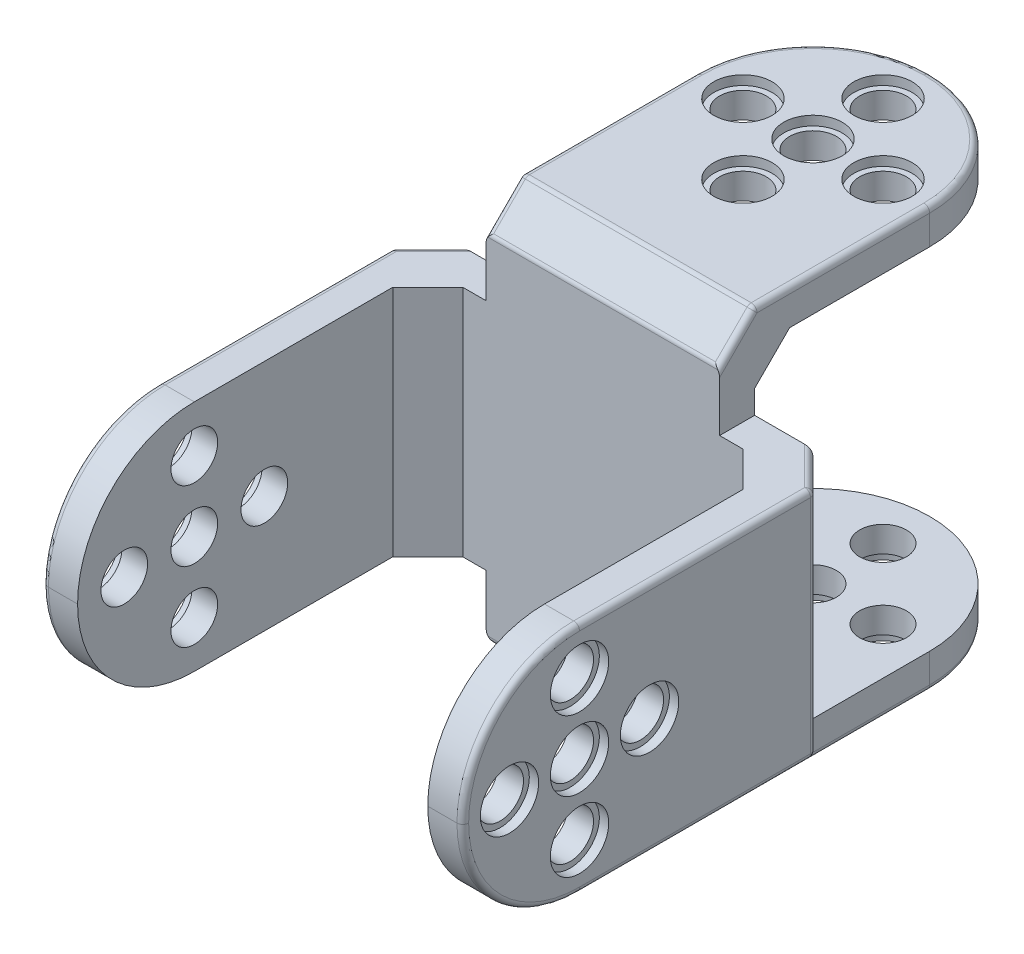
SolidWorks part; units mm, degrees
ref_plane "Front Plane" through (0, 0, 0) normal (0, 0, 1) x (1, 0, 0)
ref_plane "Top Plane" through (0, 0, 0) normal (0, 1, 0) x (1, 0, 0)
ref_plane "Right Plane" through (0, 0, 0) normal (1, 0, 0) x (0, 0, -1)
sketch "Sketch1" plane through (0, 0, 0) normal (0, 0, 1) x (1, 0, 0)
  line L1 (-18, 10) -> (18, 10)
  line L2 (-18, 10) -> (-18, -10)
  line L3 (-18, -10) -> (18, -10)
  line L4 (18, 10) -> (18, -10)
  line L5 (-18, 10) -> (18, -10) construction
  line L6 (-18, -10) -> (18, 10) construction
  line L7 (-10, -18) -> (10, -18)
  line L8 (-10, -18) -> (-10, 18)
  line L9 (-10, 18) -> (10, 18)
  line L10 (10, -18) -> (10, 18)
  line L11 (-10, -18) -> (10, 18) construction
  line L12 (-10, 18) -> (10, -18) construction
  point P0 (0, 0)
  point P6 (0, 0)
  dimension "D1" = 36
  dimension "D2" = 20
  dimension "D3" = 36
  dimension "D4" = 20
extrude "Boss-Extrude1" add sketch "Sketch1" along normal blind 3 contours L8 L9 L10 L7 | L1 L4 L3 L2
sketch "Sketch2" plane through (0, 0, 0) normal (0, 0, -1) x (-1, 0, 0)
  line L0 (10, 10) -> (10, 18) construction
  line L1 (-10, 18) -> (10, 18)
  line L2 (-10, 18) -> (-10, 15)
  line L3 (-10, 15) -> (10, 15)
  line L4 (10, 18) -> (10, 15)
  dimension "D1" = 3
extrude "Boss-Extrude2" add sketch "Sketch2" along normal blind 25
chamfer "Chamfer1" distance 3 angle 45 2 edges at (0, 18, 3)
fillet "Fillet1" radius 10 1 edges at (10, 16.5, -25)
fillet "Fillet2" radius 10 1 edges at (-10, 16.5, -25)
sketch "Sketch3" plane through (0, 18, 0) normal (0, 1, 0) x (1, 0, 0)
  line L0 (0, 25) -> (0, -10.5463) construction
  point P4 (0, 15)
  point P5 (0, 21)
  dimension "D1" = 10
  dimension "D2" = 6
hole_wizard "CBORE for M5 Hex Head Bolt1" positions "Sketch5" profile "Sketch4" counterbore size "M5" standard "DIN"
sketch "Sketch5" plane through (0, 18, 0) normal (0, 1, 0) x (1, 0, 0)
  point P0 (0, 15)
  point P3 (0, 21)
sketch "Sketch4" plane through (0, 18, -15) normal (1, 0, 0) x (0, 0, 1)
  line L0 (0, 0) -> (0, 5.1781)
  line L1 (0, 5.1781) -> (2, 4)
  line L2 (2, 4) -> (2, 0.8)
  line L3 (2, 0.8) -> (2.5, 0.8)
  line L4 (2.5, 0.8) -> (2.5, 0)
  line L5 (2.5, 0) -> (0, 0)
  line L10 (0, 5.1781) -> (-2, 4) construction
  line L11 (0, -6.35) -> (0, 107.95) construction
  dimension "Hole Dia." = 4
  dimension "Hole Depth" = 4
  dimension "C'Bore Dia." = 5
  dimension "C'Bore Depth" = 0.8
  dimension "Drill Angle" = 119
ref_axis "Axis1" through (0, 15, -15) along (0, 1, 0)
pattern_circular "CirPattern1" count 4 over 360 about axis through (0, 15, -15) along (0, 1, 0) of "CBORE for M5 Hex Head Bolt1"
mirror "Mirror1" about plane through (0, 0, 0) normal (0, 1, 0) of "Fillet1", "Fillet2", "CBORE for M5 Hex Head Bolt1", "CirPattern1", "Boss-Extrude2"
chamfer "Chamfer2" distance 3 angle 45 2 edges at (0, -18, 3) (0, -15, 0)
sketch "Sketch6" plane through (0, 0, 3) normal (0, 0, 1) x (1, 0, 0)
  line L0 (10, -10) -> (18, -10) construction
  line L1 (18, 10) -> (15, 10)
  line L2 (18, 10) -> (18, -10)
  line L3 (18, -10) -> (15, -10)
  line L4 (15, 10) -> (15, -10)
  dimension "D1" = 3
extrude "Boss-Extrude3" add sketch "Sketch6" along normal blind 30
fillet "Fillet3" radius 10 1 edges at (16.5, 10, 33)
fillet "Fillet4" radius 10 1 edges at (16.5, -10, 33)
sketch "Sketch8" plane through (18, 0, 0) normal (1, 0, 0) x (0, 0, -1)
  line L0 (-33, 0) -> (3.7503, 0) construction
  point P5 (-23, 0)
  point P6 (-29, 0)
  dimension "D1" = 10
  dimension "D2" = 6
hole_wizard "CBORE for M5 Hex Head Bolt2" positions "Sketch10" profile "Sketch9" counterbore size "M5" standard "DIN"
sketch "Sketch10" plane through (18, 0, 0) normal (1, 0, 0) x (0, 0, -1)
  point P0 (-23, 0)
  point P3 (-29, 0)
sketch "Sketch9" plane through (18, 0, 23) normal (0, 1, 0) x (0, 0, -1)
  line L0 (0, 0) -> (0, 5.1781)
  line L1 (0, 5.1781) -> (2, 4)
  line L2 (2, 4) -> (2, 0.8)
  line L3 (2, 0.8) -> (2.5, 0.8)
  line L4 (2.5, 0.8) -> (2.5, 0)
  line L5 (2.5, 0) -> (0, 0)
  line L10 (0, 5.1781) -> (-2, 4) construction
  line L11 (0, -6.35) -> (0, 107.95) construction
  dimension "Hole Dia." = 4
  dimension "Hole Depth" = 4
  dimension "C'Bore Dia." = 5
  dimension "C'Bore Depth" = 0.8
  dimension "Drill Angle" = 119
ref_axis "Axis2" through (15, 0, 23) along (1, 0, 0)
pattern_circular "CirPattern2" count 4 over 360 about axis through (15, 0, 23) along (1, 0, 0) of "CBORE for M5 Hex Head Bolt2"
chamfer "Chamfer3" distance 3 angle 45 2 edges at (18, 0, 0)
mirror "Mirror2" about plane through (0, 0, 0) normal (1, 0, 0) of "CBORE for M5 Hex Head Bolt2", "Fillet4", "Fillet3", "Boss-Extrude3", "CirPattern2"
fillet "Fillet5" radius 0.5 8 edges at (16.5, -10, 1.5) (18, -10, 13) (18, -7.0711, 30.0711) (18, 7.0711, 30.0711) (18, 10, 13) (16.5, 10, 1.5) (15, 0, 0) (18, 0, 3)
chamfer "Chamfer5" distance 3 angle 45 2 edges at (-15, 0, 3) (-18, 0, 0)
fillet "Fillet6" radius 0.5 8 edges at (-18, -10, 13) (-18, -7.0711, 30.0711) (-18, 7.0711, 30.0711) (-18, 10, 13) (-16.5, 10, 1.5) (-16.5, -10, 1.5) (-18, 0, 3) (-15, 0, 0)
fillet "Fillet7" radius 0.5 8 edges at (-7.0711, 18, -22.0711) (7.0711, 18, -22.0711) (-10, 18, -7.5) (10, 18, -7.5) (10, 16.5, 1.5) (-10, 16.5, 1.5) (0, 18, 0) (0, 15, 3)
fillet "Fillet8" radius 0.5 8 edges at (-7.0711, -18, -22.0711) (7.0711, -18, -22.0711) (-10, -18, -7.5) (10, -18, -7.5) (-10, -16.5, 1.5) (10, -16.5, 1.5) (0, -18, 0) (0, -15, 3)
